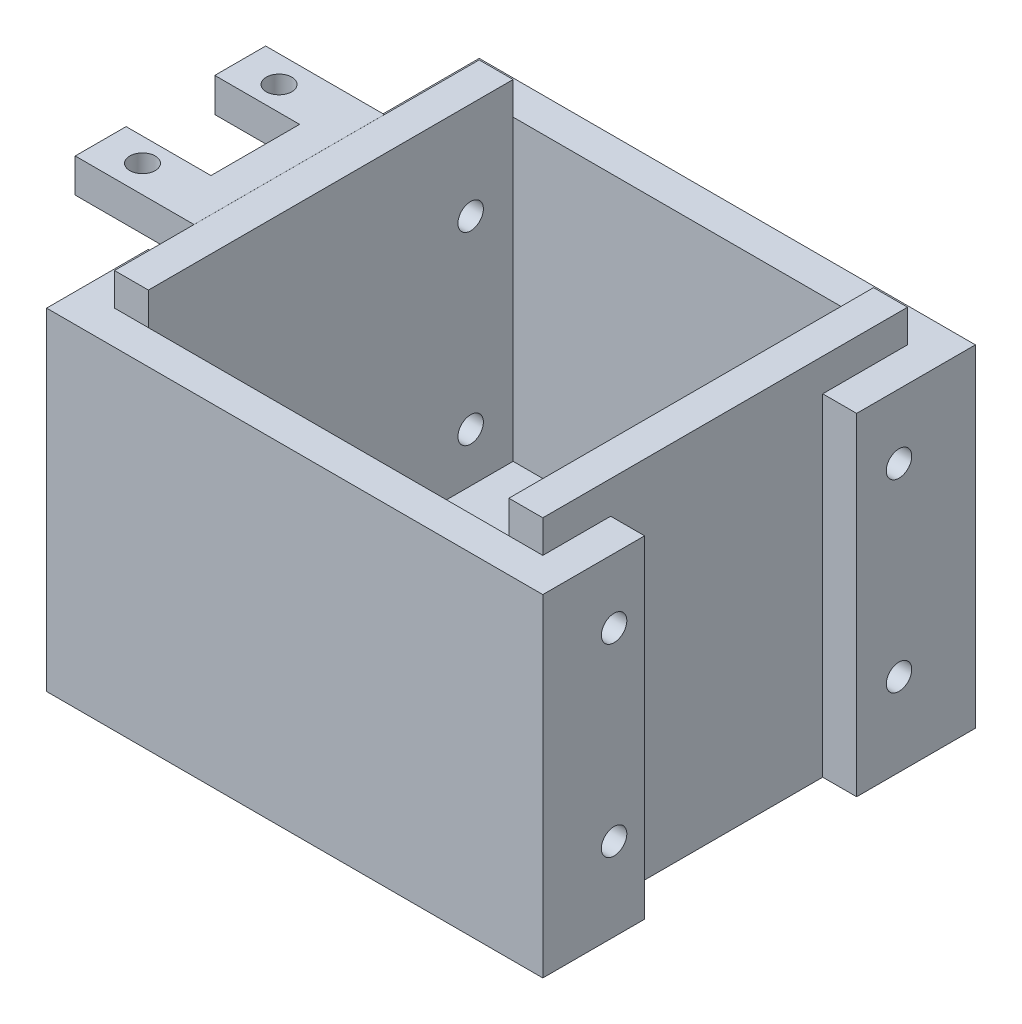
SolidWorks part; units mm, degrees
ref_plane "Front Plane" through (0, 0, 0) normal (0, 0, 1) x (1, 0, 0)
ref_plane "Top Plane" through (0, 0, 0) normal (0, 1, 0) x (1, 0, 0)
ref_plane "Right Plane" through (0, 0, 0) normal (1, 0, 0) x (0, 0, -1)
sketch "Sketch1" plane through (0, 0, 0) normal (0, 0, 1) x (1, 0, 0)
  line L0 (-21.25, -17.4937) -> (-21.25, 21.4937)
  line L1 (21.25, 21.4937) -> (21.25, -17.4937)
  line L2 (25.25, 21.4937) -> (25.25, -21.4937)
  line L3 (25.25, -21.4937) -> (-25.25, -21.4937)
  line L4 (-25.25, -21.4937) -> (-25.25, 21.4937)
  line L5 (-25.25, 21.4937) -> (-21.25, 21.4937)
  line L6 (21.25, -17.4937) -> (-21.25, -17.4937)
  line L7 (21.25, 21.4937) -> (25.25, 21.4937)
extrude "Boss-Extrude1" add sketch "Sketch1" along normal blind 43
sketch "Sketch3" plane through (0, 0, 0) normal (0, 1, 0) x (1, 0, 0)
  line L0 (-25.25, -33.6258) -> (-25.25, -11.1719)
  line L1 (-25.25, -11.1719) -> (-39.25, -11.1719)
  line L2 (-25.25, -33.6258) -> (-39.25, -33.6258)
  line L3 (-39.25, -11.1719) -> (-39.25, -17.1719)
  line L4 (-39.25, -17.1719) -> (-29.25, -17.1719)
  line L5 (-39.25, -33.6258) -> (-39.25, -27.6258)
  line L6 (-39.25, -27.6258) -> (-29.25, -27.6258)
  line L7 (-29.25, -27.6258) -> (-29.25, -17.1719)
  line L8 (-29.25, -17.1719) -> (-29.25, -11.1719)
  line L9 (-29.25, -27.6258) -> (-29.25, -33.6258)
  circle A0 centre (-34.5369, -14.3104) radius 1.5
  circle A1 centre (-34.5369, -30.4066) radius 1.5
  point P12 (-34.5369, -30.4066)
  point P14 (-25.25, -22.3989)
  point P15 (-34.7016, -15.9701)
  point P16 (-25.25, -21.5)
  point P19 (-34.7016, -27.1047)
  point P20 (-34.7016, -13.8268)
  point P21 (-34.6084, -15.1756)
  point P22 (-34.6084, -35.1546)
  point P23 (-34.25, -11.216)
  point P24 (-34.6084, -30.3967)
  point P25 (-34.6084, -31.5512)
  point P26 (-34.6084, -12.8796)
sketch "Sketch4" plane through (0, 0, 43) normal (0, 0, 1) x (1, 0, 0)
  line L0 (-25.25, 17.6538) -> (25.25, 17.6538)
  line L1 (-25.25, 21.4937) -> (-25.25, -21.4937) construction
  line L2 (25.25, -21.4937) -> (25.25, 21.4937) construction
  line L3 (25.25, 17.6538) -> (25.25, -21.4937)
  line L4 (25.25, -21.4937) -> (-25.25, -21.4937)
  line L5 (-25.25, -21.4937) -> (-25.25, 17.6538)
  line L6 (-25.25, 17.6538) -> (-29.25, 17.6538)
  line L7 (-25.25, -21.4937) -> (-29.25, -21.4937)
  line L8 (-29.25, 17.6538) -> (-29.25, 13.6538)
  line L9 (-29.25, -21.4937) -> (-29.25, -17.4937)
  line L10 (-29.25, 13.6538) -> (-29.25, -17.4937)
  line L11 (0, 0) -> (0, -4.3771)
  line L12 (25.25, 17.6538) -> (29.25, 17.6538)
  line L13 (25.25, -21.4937) -> (29.25, -21.4937)
  line L14 (29.25, 13.6538) -> (29.25, -17.4937)
  line L15 (29.25, -21.4937) -> (29.25, -17.4937)
  line L16 (29.25, 17.6538) -> (29.25, 13.6538)
  line M1 (-25.25, -21.4937) -> (25.25, -21.4937)
  line M2 (25.25, -21.4937) -> (25.25, 21.4937)
  line M4 (21.25, 21.4937) -> (21.25, -17.4937)
  line M5 (21.25, -17.4937) -> (-21.25, -17.4937)
  line M6 (-21.25, -17.4937) -> (-21.25, 21.4937)
  line M8 (-25.25, 21.4937) -> (-25.25, -21.4937)
extrude "Boss-Extrude2" add sketch "Sketch4" along normal blind 4 contours L0 | L0 M8 M1 M2 M4 M5 M6 region at (-23.25, 17.0149, 43) region at (0, 0.0801, 43)
sketch "Sketch5" plane through (0, 0, 0) normal (0, 0, -1) x (-1, 0, 0)
  line L0 (-25.25, 17.6538) -> (25.25, 17.6538)
  line L1 (25.25, 21.4937) -> (25.25, -21.4937) construction
  line L2 (25.25, 17.6538) -> (25.25, -21.4937)
  line L3 (25.25, -21.4937) -> (-25.25, -21.4937)
  line L4 (-25.25, -21.4937) -> (-25.25, 17.6538)
  line L5 (-25.25, 17.6538) -> (-29.25, 17.6538)
  line L6 (-25.25, -21.4937) -> (-29.25, -21.4937)
  line L7 (-29.25, -21.4937) -> (-29.25, 17.6538)
  line L8 (0, 0) -> (0, -3.3466)
  line L9 (25.25, -21.4937) -> (29.25, -21.4937)
  line L10 (25.25, 17.6538) -> (29.25, 17.6538)
  line L11 (29.25, -21.4937) -> (29.25, 17.6538)
  line M1 (-25.25, -21.4937) -> (25.25, -21.4937)
  line M2 (25.25, -21.4937) -> (25.25, 21.4937)
  line M4 (21.25, 21.4937) -> (21.25, -17.4937)
  line M5 (21.25, -17.4937) -> (-21.25, -17.4937)
  line M6 (-21.25, -17.4937) -> (-21.25, 21.4937)
  line M8 (-25.25, 21.4937) -> (-25.25, -21.4937)
extrude "Boss-Extrude3" add sketch "Sketch5" along normal blind 4 contours L0 | L0 M8 M1 M2 M4 M5 M6 region at (23.25, 17.0149, 0) region at (0, 0.0801, 0)
extrude "Boss-Extrude4" add sketch "Sketch3" along normal blind 17.5 and the other way blind 16 contours L7 L9 L2 L0 L1 L8 region at (-27.25, 0, 22.3989)
extrude "Boss-Extrude5" add sketch "Sketch3<3>" along normal blind 4 from surface separate body contours L4 L8 L1 L3 | L9 L6 L5 L2 region at (-34.25, 0, 33.5092) region at (-29.3666, 0, 14.1719) starting at face at (-27.25, 17.5, 22.3989)
sketch "Sketch3<3>" plane through (0, 0, 0) normal (0, 1, 0) x (1, 0, 0) same geometry as "Sketch3"
extrude "Boss-Extrude6" add sketch "Sketch3<4>" along normal blind 4 from surface contours L7 L9 L2 L0 L1 L8 region at (-27.25, 0, 22.3989) starting at face at (-27.25, 17.5, 22.3989)
sketch "Sketch3<4>" plane through (0, 0, 0) normal (0, 1, 0) x (1, 0, 0) same geometry as "Sketch3"
extrude "Boss-Extrude7" add sketch "Sketch5<3>" against normal blind 10 and the other way blind 4 contours L7 L6 L5 M8 | L9 L11 L10 M2 region at (27.25, -1.9199, 0) region at (-27.25, -1.9199, 0)
sketch "Sketch5<3>" plane through (0, 0, 0) normal (0, 0, -1) x (-1, 0, 0) same geometry as "Sketch5"
sketch "Sketch7" plane through (29.25, 0, 0) normal (1, 0, 0) x (0, 0, -1)
  circle A0 centre (-5.0057, 10.0444) radius 1.5
  circle A1 centre (-5.0057, -11.7268) radius 1.5
  point P4 (0, 0)
sketch "Sketch8" plane through (-29.25, 0, 0) normal (-1, 0, 0) x (0, 0, 1)
  circle A0 centre (5.0057, 10.0444) radius 1.5
  circle A1 centre (5.0057, -11.7268) radius 1.5
  point P6 (0, 0)
extrude "Boss-Extrude8" add sketch "Sketch4<3>" against normal blind 8 and the other way blind 4 contours L16 L12 L13 L15 L14 M2 | L8 L10 L9 L7 L6 M8 region at (-27.25, -1.9199, 43) region at (27.25, -1.9199, 43)
sketch "Sketch4<3>" plane through (0, 0, 43) normal (0, 0, 1) x (1, 0, 0) same geometry as "Sketch4"
extrude "Cut-Extrude1" cut sketch "Sketch8" against normal through all contours A1 | A0
sketch "Sketch11" plane through (-29.25, 0, 0) normal (-1, 0, 0) x (0, 0, 1)
  circle A0 centre (38.5973, 10.0444) radius 1.5
  circle A1 centre (38.5973, -11.7268) radius 1.5
  point P4 (0, 0)
extrude "Cut-Extrude2" cut sketch "Sketch11" against normal through all contours A1 | A0 region at (-29.25, -11.7268, 38.5973)
